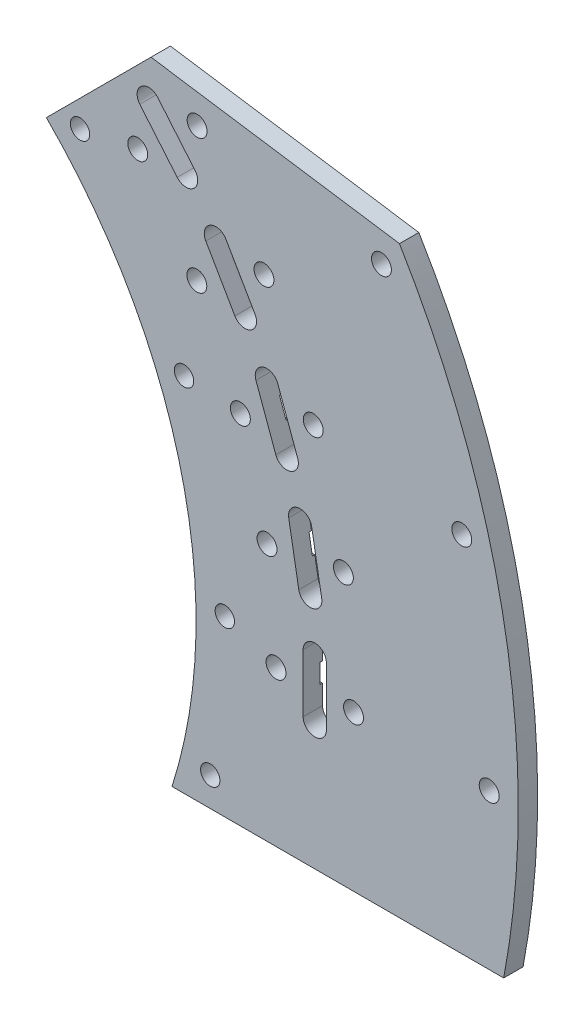
SolidWorks part; units mm, degrees
ref_plane "Front Plane" through (0, 0, 0) normal (0, 0, 1) x (1, 0, 0)
ref_plane "Top Plane" through (0, 0, 0) normal (0, 1, 0) x (1, 0, 0)
ref_plane "Right Plane" through (0, 0, 0) normal (1, 0, 0) x (0, 0, -1)
sketch "Sketch1" plane through (0, 0, 0) normal (0, 0, 1) x (1, 0, 0)
  line L0 (0, 0) -> (177.8, 0) construction
  line L1 (176.8984, 6.1774) -> (0, 0) construction
  line L2 (0, 0) -> (121.7947, 121.7947) construction
  line L3 (121.7947, 121.7947) -> (122.9173, 122.9173) construction
  line L4 (129.4542, 120.718) -> (0, 0) construction
  line L5 (0, 0) -> (163.5325, 67.7374) construction
  line L6 (167.4812, 0) -> (167.4812, -50.8) construction
  line L8 (159.5911, -50.8) -> (167.4812, -50.8) construction
  line L9 (172.1267, -41.275) -> (0, 0) construction
  line L10 (159.5911, -50.8) -> (268.2828, -50.8)
  line L11 (118.4271, 118.4271) -> (152.7152, 152.7152)
  line L12 (177.8, 0) -> (193.675, 0) construction
  line L13 (202.565, 0) -> (210.185, 0) construction
  line L14 (210.185, 0) -> (219.075, 0) construction
  line L15 (193.675, 0) -> (202.565, 0) construction
  line L16 (202.565, 0) -> (202.565, 9.525)
  line L17 (202.565, 0) -> (202.565, -9.525)
  line L18 (210.185, 9.525) -> (210.185, 0)
  line L19 (210.185, 0) -> (210.185, -9.525)
  line L20 (202.565, -9.525) -> (210.185, -9.525) construction
  line L21 (202.565, 9.525) -> (210.185, 9.525) construction
  line L22 (210.185, 9.525) -> (219.075, 0) construction
  line L23 (202.565, 9.525) -> (193.675, 0) construction
  line L24 (199.4876, 35.175) -> (201.1416, 25.7947)
  line L25 (199.4876, 35.175) -> (197.8336, 44.5553)
  line L26 (205.3378, 45.8785) -> (206.9918, 36.4982)
  line L27 (206.9918, 36.4982) -> (208.6458, 27.1179)
  line L28 (190.3488, 69.2813) -> (193.6066, 60.3307)
  line L29 (190.3488, 69.2813) -> (187.0911, 78.2319)
  line L30 (194.2516, 80.8381) -> (197.5093, 71.8875)
  line L31 (197.5093, 71.8875) -> (200.767, 62.9369)
  line L32 (175.4264, 101.2825) -> (180.1889, 93.0336)
  line L33 (175.4264, 101.2825) -> (170.6639, 109.5314)
  line L34 (177.263, 113.3414) -> (182.0255, 105.0925)
  line L35 (182.0255, 105.0925) -> (186.788, 96.8436)
  line L36 (155.1738, 130.2063) -> (161.2963, 122.9097)
  line L37 (155.1738, 130.2063) -> (149.0512, 137.5028)
  line L38 (154.8885, 142.4009) -> (161.0111, 135.1043)
  line L39 (161.0111, 135.1043) -> (167.1336, 127.8077)
  line L40 (0, 0) -> (193.675, 0) construction
  line L41 (0, 0) -> (190.7326, 33.6313) construction
  line L42 (0, 0) -> (254, 0) construction
  line L43 (254, 0) -> (263.525, 0) construction
  line L44 (254.5456, 68.2053) -> (0, 0) construction
  line L45 (152.7152, 152.7152) -> (234.123, 140.5088)
  line L46 (167.8212, 140.8187) -> (228.2193, 131.7625) construction
  line L47 (254.5456, 68.2053) -> (263.746, 70.6705) construction
  arc A0 (172.2437, 0) -> (121.7947, 121.7947) centre (0, 0) ccw construction
  arc A1 (173.8312, 0) -> (122.9173, 122.9173) centre (0, 0) ccw construction
  circle A2 centre (176.8984, 6.1774) radius 3.175
  circle A3 centre (129.4542, 120.718) radius 3.175
  circle A4 centre (163.5325, 67.7374) radius 3.175
  arc A5 (167.4812, 0) -> (118.4271, 118.4271) centre (0, 0) ccw
  arc A6 (167.4812, 0) -> (159.5911, -50.8) centre (0, 0) cw
  arc A7 (173.8312, 0) -> (166.2428, -50.8) centre (0, 0) cw construction
  circle A8 centre (172.1267, -41.275) radius 3.175
  circle A9 centre (193.675, 0) radius 9.525 construction
  circle A10 centre (219.075, 0) radius 9.525 construction
  arc A11 (202.565, -9.525) -> (210.185, -9.525) centre (206.375, -9.525) ccw
  arc A12 (202.565, 9.525) -> (210.185, 9.525) centre (206.375, 9.525) cw
  circle A13 centre (193.675, 0) radius 3.2639
  circle A14 centre (219.075, 0) radius 3.2639
  circle A15 centre (215.7468, 38.042) radius 3.2639
  arc A16 (201.1416, 25.7947) -> (208.6458, 27.1179) centre (204.8937, 26.4563) ccw
  arc A17 (197.8336, 44.5553) -> (205.3378, 45.8785) centre (201.5857, 45.2169) cw
  circle A18 centre (190.7326, 33.6313) radius 3.2639
  circle A19 centre (205.8632, 74.9281) radius 3.2639
  arc A20 (193.6066, 60.3307) -> (200.767, 62.9369) centre (197.1868, 61.6338) ccw
  arc A21 (187.0911, 78.2319) -> (194.2516, 80.8381) centre (190.6713, 79.535) cw
  circle A22 centre (181.995, 66.2408) radius 3.2639
  circle A23 centre (189.7245, 109.5375) radius 3.2639
  arc A24 (180.1889, 93.0336) -> (186.788, 96.8436) centre (183.4885, 94.9386) ccw
  arc A25 (170.6639, 109.5314) -> (177.263, 113.3414) centre (173.9635, 111.4364) cw
  circle A26 centre (167.7275, 96.8375) radius 3.2639
  circle A27 centre (167.8212, 140.8187) radius 3.2639
  arc A28 (161.2963, 122.9097) -> (167.1336, 127.8077) centre (164.215, 125.3587) ccw
  arc A29 (149.0512, 137.5028) -> (154.8885, 142.4009) centre (151.9699, 139.9519) cw
  circle A30 centre (148.3637, 124.4919) radius 3.2639
  circle A31 centre (263.525, 0) radius 3.2639
  circle A32 centre (254.5456, 68.2053) radius 3.2639
  circle A33 centre (228.2193, 131.7625) radius 3.2639
  arc A34 (234.123, 140.5088) -> (268.2828, -50.8) centre (0, 0) cw
  point P3 (172.2437, 0)
  point P96 (0, 0)
  dimension "D3" = 1.5875
  dimension "D4" = 6.35
  dimension "D5" = 2
  dimension "D7" = 2
  dimension "D8" = 6.35
  dimension "D9" = 6.35
  dimension "D11" = 6.35
  dimension "D13" = 6.35
  dimension "D15" = 19.05
  dimension "D16" = 7.62
  dimension "D17" = 19.05
  dimension "D21" = 15.875
  dimension "D22" = 6.5278
  dimension "D23" = 6.5278
  dimension "D28" = 6.5278
  dimension "D32" = 9.525
  dimension "D1" = 177.8
  dimension "D2" = 5.5562
  dimension "D6" = 45
  dimension "D10" = 22.5
  dimension "D12" = 50.8
  dimension "D14" = 9.525
  dimension "D18" = 9.525
  dimension "D19" = 9.525
  dimension "D20" = 25.4
  dimension "D25" = 10
  dimension "D26" = 254
  dimension "D27" = 9.525
  dimension "D30" = 15
  dimension "D31" = 9.525
  dimension "D24" = 5
  dimension "D29" = 3
extrude "Boss-Extrude1" add sketch "Sketch1" along normal blind 6.35 contours A34 L45 L11 A5 A6 L10 A33 A32 A31 A30 A27 A26 A23 A22 A19 A18 A15 A14 A13 A8 A4 A3 A2 L16 A12 L18 L19 A11 L17 L25 A17 L26 region at (208.105, 48.0367, 0)
sketch "Sketch2" plane through (0, 0, 0) normal (0, 0, 1) x (1, 0, 0)
  line L0 (202.565, -9.525) -> (202.565, 9.525) construction
  line L1 (210.185, 9.525) -> (210.185, -9.525) construction
  line L2 (0, 0) -> (202.565, 0) construction
  line L3 (0, 0) -> (199.4876, 35.175) construction
  circle A0 centre (202.565, 0) radius 3.175
  circle A1 centre (210.185, 0) radius 3.175
  circle A2 centre (199.4876, 35.175) radius 3.175
  circle A3 centre (206.9918, 36.4982) radius 3.175
  circle A4 centre (190.3488, 69.2813) radius 3.175
  circle A5 centre (197.5093, 71.8875) radius 3.175
  circle A6 centre (175.4264, 101.2825) radius 3.175
  circle A7 centre (182.0255, 105.0925) radius 3.175
  circle A8 centre (155.1738, 130.2063) radius 3.175
  circle A9 centre (161.0111, 135.1043) radius 3.175
  dimension "D1" = 6.35
  dimension "D2" = 6.35
  dimension "D4" = 10
  dimension "D3" = 5
extrude "Cut-Extrude1" cut sketch "Sketch2" along normal blind 0.7937
